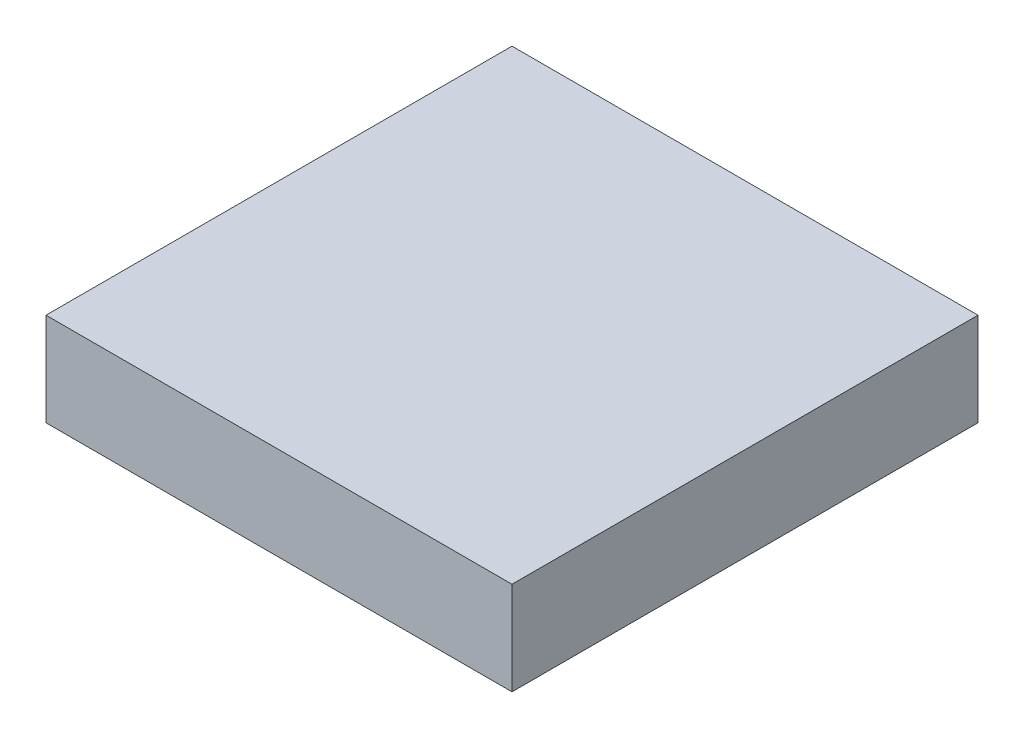
SolidWorks part; units mm, degrees
material "Oak"
ref_plane "Front Plane" through (0, 0, 0) normal (0, 0, 1) x (1, 0, 0)
ref_plane "Top Plane" through (0, 0, 0) normal (0, 1, 0) x (1, 0, 0)
ref_plane "Right Plane" through (0, 0, 0) normal (1, 0, 0) x (0, 0, -1)
sketch "Sketch1" plane through (0, 0, 0) normal (0, 1, 0) x (1, 0, 0)
  line L1 (-75, 75) -> (75, 75)
  line L2 (-75, 75) -> (-75, -75)
  line L3 (-75, -75) -> (75, -75)
  line L4 (75, 75) -> (75, -75)
  line L5 (-75, 75) -> (75, -75) construction
  line L6 (-75, -75) -> (75, 75) construction
  point P0 (0, 0)
  dimension "D1" = 150
  dimension "D2" = 150
extrude "Boss-Extrude1" add sketch "Sketch1" along normal blind 30
shell "Shell1" thickness 7.5 removed face at (0, 0, 0)
